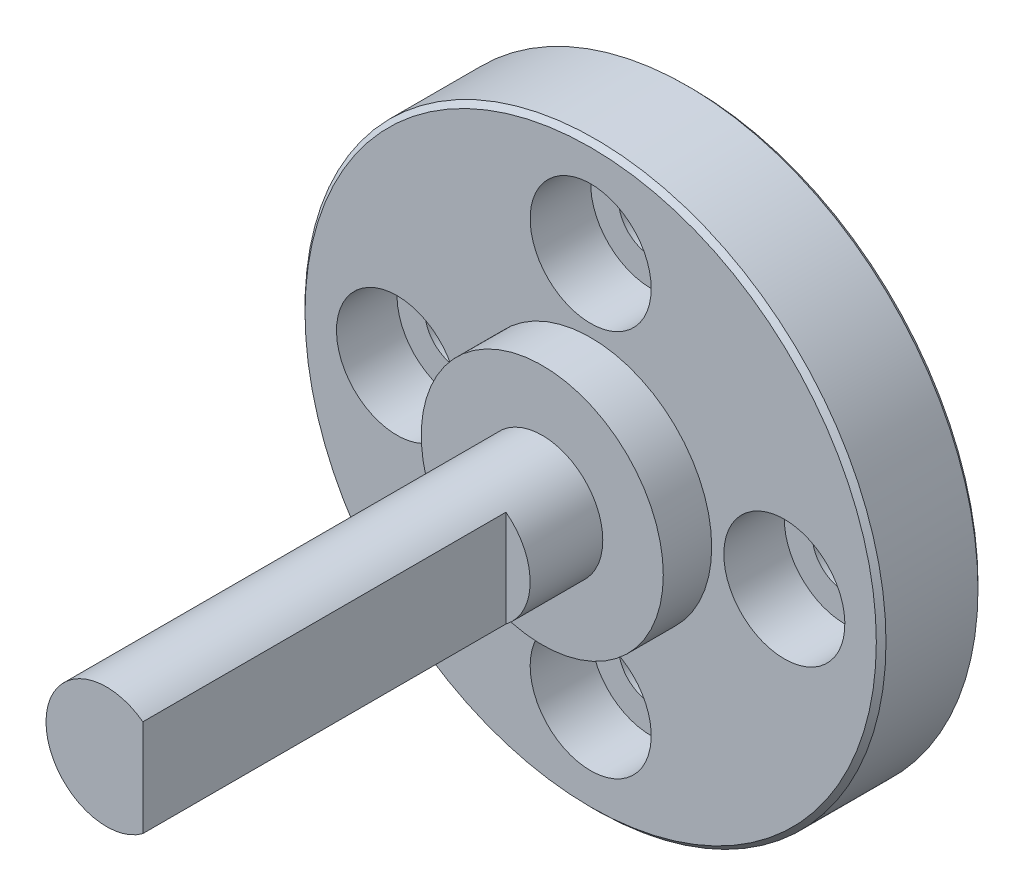
SolidWorks part; units mm, degrees
material "PA(尼龙6)"
ref_plane "前视基准面" through (0, 0, 0) normal (0, 0, 1) x (1, 0, 0)
ref_plane "上视基准面" through (0, 0, 0) normal (0, 1, 0) x (1, 0, 0)
ref_plane "右视基准面" through (0, 0, 0) normal (1, 0, 0) x (0, 0, -1)
sketch "草图1" plane through (0, 0, 0) normal (0, 0, 1) x (1, 0, 0)
  circle A3 centre (0, 0) radius 3
  circle A4 centre (0, 0) radius 12
  point P7 (0, 0)
  dimension "D1" = 24
  dimension "D2" = 6
extrude "凸台-拉伸1" add sketch "草图1" along normal blind 4.2 contours A3 | A4 A3 region at (0, 0, 0) region at (-11.6606, 0, 0)
sketch "草图2" plane through (0, 0, 4.2) normal (0, 0, 1) x (1, 0, 0)
  circle A0 centre (0, 0) radius 5
  dimension "D1" = 10
extrude "凸台-拉伸2" add sketch "草图2" along normal blind 2
hole_wizard "M2.5 六角圆柱头螺钉的柱形沉头孔1" positions "草图8" profile "草图9" counterbore size "M2.5" standard "GB" end condition through all
sketch "草图8" plane through (0, 0, 4.2) normal (0, 0, 1) x (1, 0, 0)
  line L0 (0, 0) -> (0, 8) construction
  point P0 (0, 8)
  dimension "D1" = 8
sketch "草图9" plane through (0, 8, 4.2) normal (1, 0, 0) x (0, -1, 0)
  line L0 (0, 0) -> (0, 4.2)
  line L1 (0, 4.2) -> (1.35, 4.2)
  line L3 (1.35, 4.2) -> (1.35, 2.5)
  line L4 (1.35, 2.5) -> (2.5, 2.5)
  line L5 (2.5, 2.5) -> (2.5, 0)
  line L7 (2.5, 0) -> (0, 0)
  line L11 (0, -6.35) -> (0, 107.95) construction
  dimension "通孔孔直径" = 2.7
  dimension "通孔孔深度" = 4.2
  dimension "柱形沉头孔直径" = 5
  dimension "柱形沉头孔深度" = 2.5
pattern_circular "阵列(圆周)1" count 4 over 360 about axis through (0, 0, 4.2) along (0, 0, -1) of "M2.5 六角圆柱头螺钉的柱形沉头孔1"
chamfer "倒角3" distance 0.2 angle 45 2 edges at (12, 0, 0) (12, 0, 4.2)
sketch "草图12" plane through (0, 0, 4.2) normal (0, 0, 1) x (1, 0, 0)
  circle A0 centre (0, 0) radius 2.5
  dimension "D1" = 5
extrude "轴" add sketch "草图12" along normal blind 20
sketch "草图13" plane through (0, 0, 24.2) normal (0, 0, 1) x (1, 0, 0)
  line L0 (0, 0) -> (4.1196, 0) construction
  line L1 (1.5, 2.6158) -> (1.5, -2.6158)
  circle A0 centre (0, 0) radius 2.5 construction
  circle A1 centre (0, 0) radius 2.5
  point P6 (1.5, 0)
  circle M2 centre (0, 0) radius 2.5
  dimension "D1" = 1.5
extrude "切除-拉伸1" cut sketch "草图13" against normal blind 15 contours L0 L1 M2 | L1 L0 A1 region at (1.9078, 0.775, 24.2) region at (1.9078, -0.775, 24.2)
